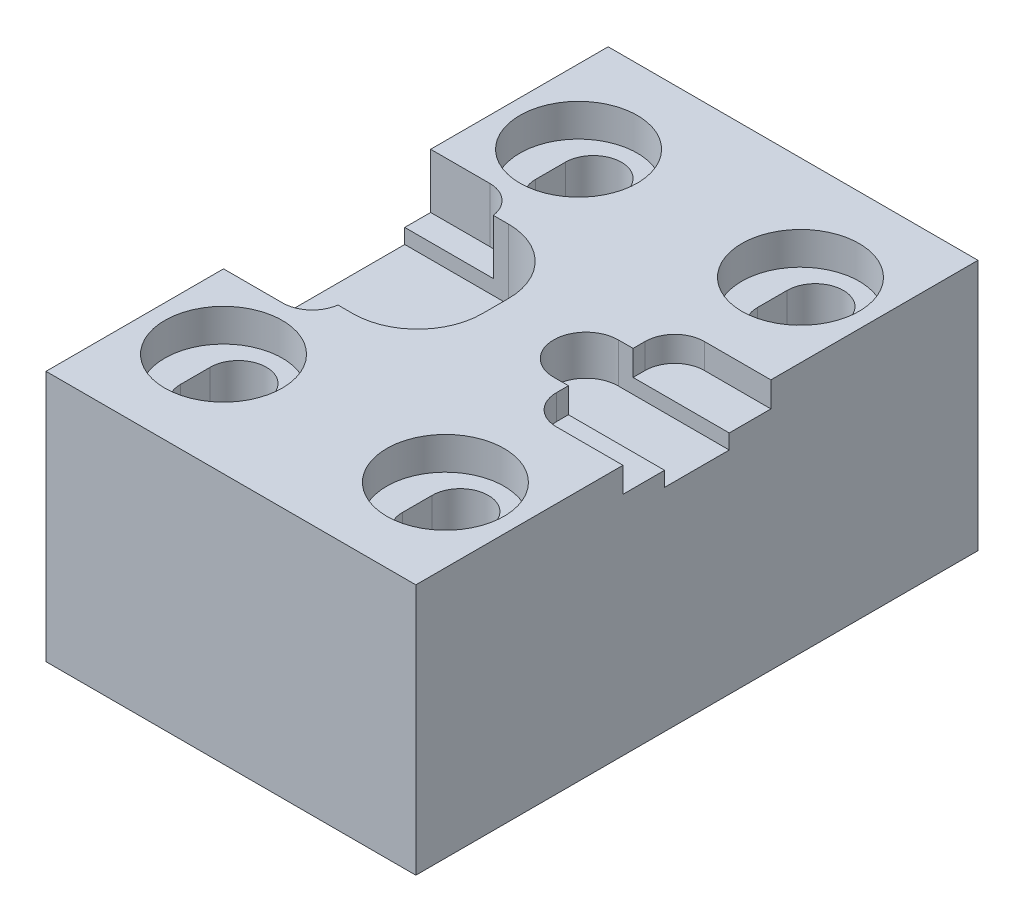
SolidWorks part; units mm, degrees
material "6063-T5"
ref_plane "Front Plane" through (0, 0, 0) normal (0, 0, 1) x (1, 0, 0)
ref_plane "Top Plane" through (0, 0, 0) normal (0, 1, 0) x (1, 0, 0)
ref_plane "Right Plane" through (0, 0, 0) normal (1, 0, 0) x (0, 0, -1)
sketch "Sketch1" plane through (0, 0, 0) normal (0, 1, 0) x (1, 0, 0)
  line L1 (-18493.9467, 11317.1913) -> (-18468.9467, 11317.1913)
  line L2 (-18493.9467, 11317.1913) -> (-18493.9467, 11279.1913)
  line L3 (-18493.9467, 11279.1913) -> (-18468.9467, 11279.1913)
  line L4 (-18468.9467, 11317.1913) -> (-18468.9467, 11279.1913)
  dimension "D1" = 25
  dimension "D2" = 38
extrude "Boss-Extrude1" add sketch "Sketch1" along normal blind 17
sketch "Sketch2" plane through (0, 17, 0) normal (0, 1, 0) x (1, 0, 0)
  line L0 (-18493.9467, 11298.1913) -> (-18468.9467, 11298.1913)
  line L1 (-18493.9467, 11317.1913) -> (-18493.9467, 11279.1913) construction
  line L2 (-18468.9467, 11279.1913) -> (-18468.9467, 11317.1913) construction
  line L3 (-18491.9467, 11305.1913) -> (-18493.9467, 11305.1913)
  line L4 (-18489.9467, 11291.1913) -> (-18491.9467, 11291.1913)
  line L5 (-18487.9467, 11293.1913) -> (-18487.9467, 11303.1913)
  line L6 (-18489.9467, 11305.1913) -> (-18491.9467, 11305.1913)
  line L7 (-18493.9467, 11300.1913) -> (-18493.9467, 11314.1913)
  line L8 (-18487.9467, 11291.1913) -> (-18493.9467, 11305.1913) construction
  line L9 (-18487.9467, 11305.1913) -> (-18493.9467, 11291.1913) construction
  line L10 (-18470.9467, 11293.1913) -> (-18473.4467, 11293.1913)
  line L11 (-18468.9467, 11293.1913) -> (-18468.9467, 11303.1913)
  line L12 (-18470.9467, 11303.1913) -> (-18473.4467, 11303.1913)
  line L13 (-18475.4467, 11295.1913) -> (-18475.4467, 11301.1913)
  line L14 (-18468.9467, 11293.1913) -> (-18475.4467, 11303.1913) construction
  line L15 (-18468.9467, 11303.1913) -> (-18475.4467, 11293.1913) construction
  line L16 (-18491.9467, 11291.1913) -> (-18493.9467, 11291.1913)
  line L17 (-18470.9467, 11303.1913) -> (-18468.9467, 11303.1913)
  line L18 (-18470.9467, 11293.1913) -> (-18468.9467, 11293.1913)
  line L19 (-18488.9467, 11286.1913) -> (-18488.9467, 11310.1913)
  line L20 (-18488.9467, 11286.1913) -> (-18473.9467, 11286.1913)
  line L21 (-18488.9467, 11310.1913) -> (-18473.9467, 11310.1913)
  line L22 (-18473.9467, 11286.1913) -> (-18473.9467, 11310.1913)
  line L23 (-18488.9467, 11286.1913) -> (-18473.9467, 11310.1913) construction
  line L24 (-18488.9467, 11310.1913) -> (-18473.9467, 11286.1913) construction
  arc A0 (-18489.9467, 11291.1913) -> (-18487.9467, 11293.1913) centre (-18489.9467, 11293.1913) ccw
  arc A1 (-18487.9467, 11303.1913) -> (-18489.9467, 11305.1913) centre (-18489.9467, 11303.1913) ccw
  arc A5 (-18473.4467, 11303.1913) -> (-18475.4467, 11301.1913) centre (-18473.4467, 11301.1913) ccw
  arc A6 (-18473.4467, 11293.1913) -> (-18475.4467, 11295.1913) centre (-18473.4467, 11295.1913) cw
  point P6 (-18490.9467, 11298.1913)
  point P11 (-18472.1967, 11298.1913)
  point P16 (-18492.9467, 11291.1913)
  point P25 (-18481.4467, 11298.1913)
  point P27 (0, 0)
  line M12 (-18493.9467, 11317.1913) -> (-18493.9467, 11279.1913)
  dimension "D7" = 2
  dimension "D8" = 5
  dimension "D9" = 5
  dimension "D10" = 5
  dimension "D1" = 12.5
  dimension "D2" = 0
  dimension "D3" = 6
  dimension "D4" = 0
  dimension "D5" = 10
  dimension "D6" = 14
  dimension "D11" = 5
extrude "Cut-Extrude3" cut sketch "Sketch2" against normal offset from surface (3.7 mm away) 13.3 contours L5 A1 L6 L3 L0 M12 | L4 A0 L5 L0 L16 M12 | L5 A1 L19 L0 | L19 A0 L5 L0 region at (-18491.4523, 17, -11301.6828) region at (-18491.4523, 17, -11294.6998) region at (-18488.4645, 17, -11301.3181) region at (-18488.4645, 17, -11295.0644) up to face at (-18481.4467, 0, -11298.1913)
extrude "Cut-Extrude4" cut sketch "Sketch2<6>" against normal offset from surface (1.7 mm away) 15.3 contours L12 A5 L13 L0 L11 | A6 L10 L11 L0 L13 | L22 A5 L13 L0 | A6 L22 L0 L13 region at (-18474.6562, 17, -11300.4302) region at (-18474.6562, 17, -11295.9523) region at (-18471.4457, 17, -11300.6902) region at (-18471.4457, 17, -11295.6923) up to face at (-18481.4467, 0, -11298.1913)
sketch "Sketch2<6>" plane through (0, 17, 0) normal (0, 1, 0) x (1, 0, 0) same geometry as "Sketch2"
hole_wizard "CBORE for #6 Binding Head Machine Screw1" positions "Sketch10" profile "Sketch11" counterbore size "#6" standard "ANSI Inch" end condition through all
sketch "Sketch10" plane through (0, 17, 0) normal (0, 1, 0) x (1, 0, 0)
  point P0 (-18488.9467, 11310.1913)
  point P3 (-18473.9467, 11310.1913)
  point P6 (-18473.9467, 11286.1913)
  point P9 (-18488.9467, 11286.1913)
sketch "Sketch11" plane through (-18488.9467, 17, -11310.1913) normal (1, 0, 0) x (0, 0, 1)
  line L0 (0, 0) -> (0, 17)
  line L1 (0, 17) -> (1.8986, 17)
  line L3 (1.8986, 17) -> (1.8986, 2.2098)
  line L4 (1.8986, 2.2098) -> (3.9687, 2.2098)
  line L5 (3.9687, 2.2098) -> (3.9687, 0)
  line L7 (3.9687, 0) -> (0, 0)
  line L11 (0, -6.35) -> (0, 107.95) construction
  dimension "Thru Hole Dia." = 3.7973
  dimension "Thru Hole Depth" = 17
  dimension "C'Bore Dia." = 7.9375
  dimension "C'Bore Depth" = 2.2098
sketch "Sketch12" plane through (0, 17, 0) normal (0, 1, 0) x (1, 0, 0)
  line L0 (-18468.9467, 11293.1913) -> (-18468.9467, 11303.1913) construction
  line L1 (-18476.4467, 11300.3763) -> (-18468.9467, 11300.3763)
  line L2 (-18476.4467, 11300.3763) -> (-18476.4467, 11296.0063)
  line L3 (-18476.4467, 11296.0063) -> (-18468.9467, 11296.0063)
  line L4 (-18468.9467, 11300.3763) -> (-18468.9467, 11296.0063)
  line L5 (-18493.9467, 11298.1913) -> (-18468.9467, 11298.1913) construction
  line L6 (-18487.9467, 11293.1913) -> (-18487.9467, 11303.1913) construction
  arc A0 (-18476.4467, 11300.3763) -> (-18476.4467, 11296.0063) centre (-18476.4467, 11298.1913) ccw
  point P6 (-18476.4467, 11298.1913)
  line M20 (-18475.4467, 11295.1913) -> (-18475.4467, 11301.1913)
  dimension "D1" = 0
  dimension "D2" = 4.37
  dimension "D3" = 11.5
extrude "Cut-Extrude5" cut sketch "Sketch12" against normal offset from surface (2.7 mm away) 14.3 contours L2 A0 | L2 L3 L1 M20 | L4 L1 L3 M20 region at (-18475.9467, 17, -11298.1913) region at (-18477.3741, 17, -11298.1913) region at (-18472.1967, 17, -11298.1913) up to face at (-18488.9467, 0, -11308.2926)
sketch "Sketch13" plane through (0, 17, 0) normal (0, 1, 0) x (1, 0, 0)
  line L0 (-18493.9467, 11291.1913) -> (-18493.9467, 11305.1913) construction
  line L1 (-18486.9467, 11303.4413) -> (-18493.9467, 11303.4413)
  line L2 (-18486.9467, 11303.4413) -> (-18486.9467, 11292.9413)
  line L3 (-18486.9467, 11292.9413) -> (-18493.9467, 11292.9413)
  line L4 (-18493.9467, 11303.4413) -> (-18493.9467, 11292.9413)
  line L5 (-18493.9467, 11298.1913) -> (-18468.9467, 11298.1913) construction
  line L6 (-18487.9467, 11293.1913) -> (-18487.9467, 11303.1913) construction
  line L8 (-18486.9467, 11303.4413) -> (-18486.9367, 11303.4413)
  line L9 (-18486.9467, 11303.4413) -> (-18486.9467, 11292.9413)
  line L10 (-18486.9467, 11292.9413) -> (-18486.9367, 11292.9413)
  line L11 (-18482.5767, 11299.0813) -> (-18482.5767, 11297.3013)
  arc A0 (-18486.9367, 11292.9413) -> (-18482.5767, 11297.3013) centre (-18486.9367, 11297.3013) ccw
  arc A1 (-18486.9367, 11303.4413) -> (-18482.5767, 11299.0813) centre (-18486.9367, 11299.0813) cw
  point P6 (-18486.9467, 11298.1913)
  point P17 (-18482.5767, 11303.4413)
  arc M19 (-18489.9467, 11305.1913) -> (-18487.9467, 11303.1913) centre (-18489.9467, 11303.1913) cw
  line M20 (-18487.9467, 11303.1913) -> (-18487.9467, 11293.1913)
  arc M21 (-18487.9467, 11293.1913) -> (-18489.9467, 11291.1913) centre (-18489.9467, 11293.1913) cw
  dimension "D5" = 4.36
  dimension "D1" = 0
  dimension "D2" = 10.5
  dimension "D3" = 1
  dimension "D4" = 4.37
extrude "Cut-Extrude6" cut sketch "Sketch13" against normal offset from surface (4.7 mm away) 12.3 contours A1 L8 L2 L10 A0 L11 | L1 L4 L3 M21 M20 M19 | L3 L2 L1 M19 M20 M21 region at (-18487.4469, 17, -11298.1913) region at (-18485.0237, 17, -11298.1913) region at (-18490.9469, 17, -11298.1913) up to face at (-18488.9467, 0, -11308.2926)
sketch "Sketch14" plane through (0, 17, 0) normal (0, 1, 0) x (1, 0, 0)
  line L0 (-18488.9467, 11309.1913) -> (-18488.9467, 11311.1913) construction
  line L1 (-18490.8467, 11309.1913) -> (-18490.8467, 11311.1913)
  line L2 (-18487.0467, 11309.1913) -> (-18487.0467, 11311.1913)
  line L3 (-18481.4467, 11317.1913) -> (-18481.4467, 11279.1913)
  line L4 (-18468.9467, 11317.1913) -> (-18493.9467, 11317.1913) construction
  line L5 (-18493.9467, 11279.1913) -> (-18468.9467, 11279.1913) construction
  line L6 (-18473.9467, 11309.1913) -> (-18473.9467, 11311.1913) construction
  line L7 (-18472.0467, 11309.1913) -> (-18472.0467, 11311.1913)
  line L8 (-18475.8467, 11309.1913) -> (-18475.8467, 11311.1913)
  line L9 (-18493.9467, 11298.1913) -> (-18468.9467, 11298.1913)
  line L10 (-18473.9467, 11287.1913) -> (-18473.9467, 11285.1913) construction
  line L11 (-18472.0467, 11287.1913) -> (-18472.0467, 11285.1913)
  line L12 (-18475.8467, 11287.1913) -> (-18475.8467, 11285.1913)
  line L13 (-18488.9467, 11287.1913) -> (-18488.9467, 11285.1913) construction
  line L14 (-18490.8467, 11287.1913) -> (-18490.8467, 11285.1913)
  line L15 (-18487.0467, 11287.1913) -> (-18487.0467, 11285.1913)
  arc A0 (-18490.8467, 11309.1913) -> (-18487.0467, 11309.1913) centre (-18488.9467, 11309.1913) ccw
  arc A1 (-18487.0467, 11311.1913) -> (-18490.8467, 11311.1913) centre (-18488.9467, 11311.1913) ccw
  arc A2 (-18472.0467, 11309.1913) -> (-18475.8467, 11309.1913) centre (-18473.9467, 11309.1913) cw
  arc A3 (-18475.8467, 11311.1913) -> (-18472.0467, 11311.1913) centre (-18473.9467, 11311.1913) cw
  arc A4 (-18472.0467, 11287.1913) -> (-18475.8467, 11287.1913) centre (-18473.9467, 11287.1913) ccw
  arc A5 (-18475.8467, 11285.1913) -> (-18472.0467, 11285.1913) centre (-18473.9467, 11285.1913) ccw
  arc A6 (-18490.8467, 11287.1913) -> (-18487.0467, 11287.1913) centre (-18488.9467, 11287.1913) cw
  arc A7 (-18487.0467, 11285.1913) -> (-18490.8467, 11285.1913) centre (-18488.9467, 11285.1913) cw
  point P3 (-18488.9467, 11310.1913)
  point P18 (-18473.9467, 11310.1913)
  point P29 (-18473.9467, 11286.1913)
  point P36 (-18488.9467, 11286.1913)
  dimension "D1" = 2
  dimension "D2" = 3.8
extrude "Cut-Extrude7" cut sketch "Sketch14" against normal through all contours L2 A1 L1 A0 | A3 L8 A2 L7 | A7 L15 A6 L14 | L12 A5 L11 A4 region at (-18488.9467, 17, -11310.1913) region at (-18473.9467, 17, -11310.1913) region at (-18473.9467, 17, -11286.1913) region at (-18488.9467, 17, -11286.1913)
